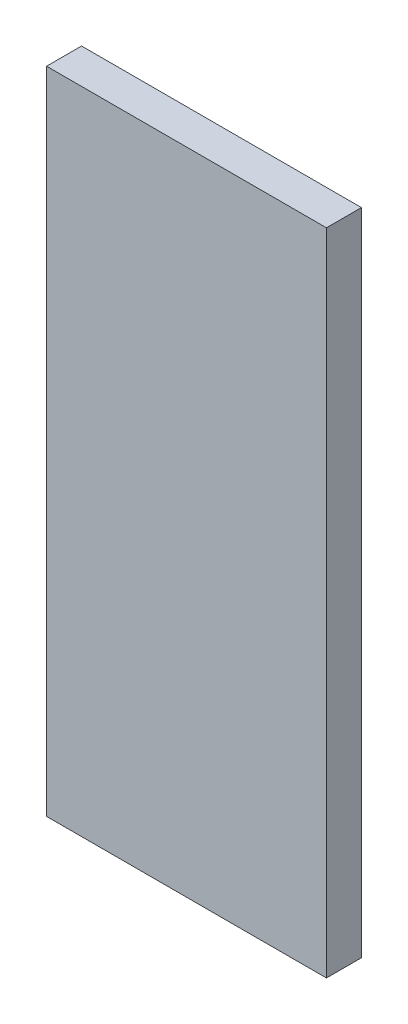
SolidWorks part; units mm, degrees
ref_plane "Ön Düzlem" through (0, 0, 0) normal (0, 0, 1) x (1, 0, 0)
ref_plane "Üst Düzlem" through (0, 0, 0) normal (0, 1, 0) x (1, 0, 0)
ref_plane "Sağ Düzlem" through (0, 0, 0) normal (1, 0, 0) x (0, 0, -1)
sketch "Çizim1" plane through (0, 0, 0) normal (0, 0, 1) x (1, 0, 0)
  line L1 (0, 0) -> (280, 0)
  line L2 (0, 0) -> (0, -650)
  line L3 (0, -650) -> (280, -650)
  line L4 (280, 0) -> (280, -650)
  dimension "D1" = 280
  dimension "D2" = 650
base flange "Taban-Flanş1" sketch "Çizim1" thickness 35 reverse thickness direction no parameters "D1"=5
sketch "Büküm-Çizgileri1" [suppressed] plane through (0, 0, 0) normal (0, 1, 0) x (1, 0, 0)
sketch "Sınırlandırma-Kutusu1" [suppressed] plane through (0, 0, 0) normal (0, 1, 0) x (1, 0, 0)
sheet metal parameters "Sac-Levha1" thickness 35 parameters "D1"=5
flat pattern "Düz-Çoğaltma1" [suppressed]
sketch "Büküm-Çizgileri2" plane through (0, 0, 0) normal (0, 1, 0) x (1, 0, 0)
sketch3d "Sınırlandırma-Kutusu2" [suppressed]
  line L0 (280, 0, 0) -> (280, -650, 0) construction
  line L1 (0, 0, 0) -> (0, -650, 0) construction
  line L2 (280, 0, 0) -> (0, 0, 0) construction
  line L3 (280, -650, 0) -> (0, -650, 0) construction
